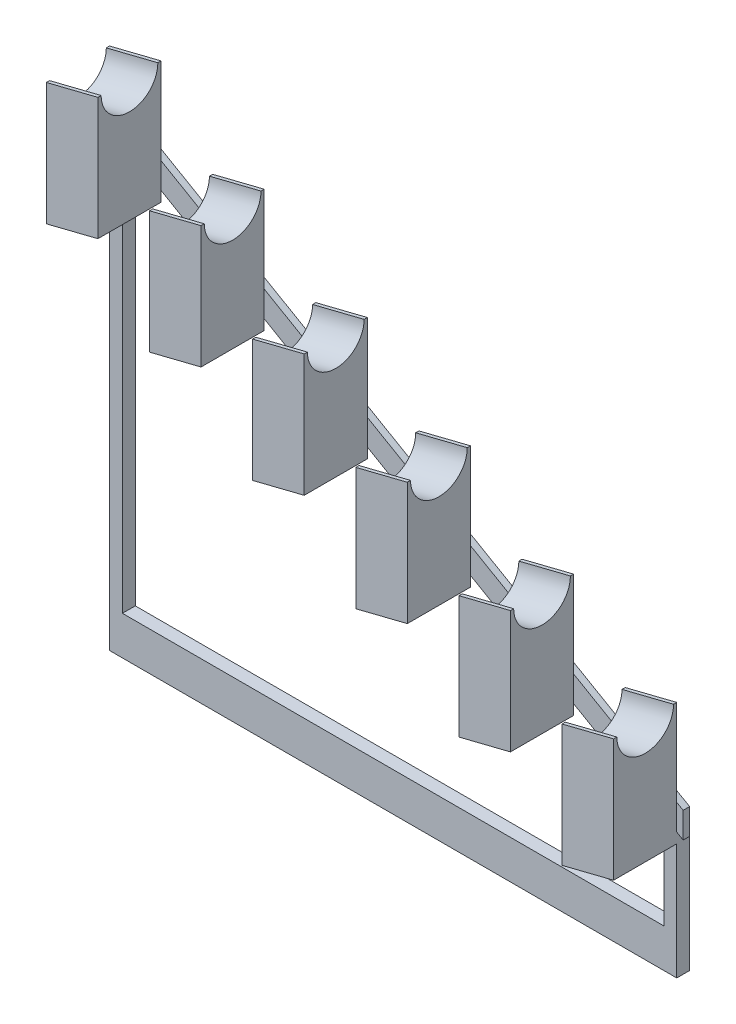
SolidWorks part; units mm, degrees
ref_plane "Front Plane" through (0, 0, 0) normal (0, 0, 1) x (1, 0, 0)
ref_plane "Top Plane" through (0, 0, 0) normal (0, 1, 0) x (1, 0, 0)
ref_plane "Right Plane" through (0, 0, 0) normal (1, 0, 0) x (0, 0, -1)
sketch "Sketch2" plane through (0, 0, 0) normal (1, 0, 0) x (0, 0, -1)
  line L2 (0, 0) -> (0, -84.6928) construction
  line L7 (-24.5, 0) -> (-22, 0)
  line L9 (-24.5, 0) -> (-24.5, -95)
  line L10 (-24.5, -95) -> (24.5, -95)
  line L11 (24.5, 0) -> (24.5, -95)
  line L12 (22, 0) -> (24.5, 0)
  arc A0 (-22, 0) -> (22, 0) centre (0, 0) ccw
  dimension "D1" = 22
  dimension "D3" = 95
  dimension "D4" = 2.5
  dimension "D2" = 49
  dimension "D5" = 2.5
sketch "Sketch3" plane through (0, 0, 0) normal (0, 0, 1) x (1, 0, 0)
  line L0 (0, 0) -> (-40, -10)
  dimension "D1" = 40
  dimension "D2" = 10
sweep "Sweep1" add profiles "Sketch2" path "Sketch3"
ref_plane "Plane2" through (0, -105, 0) normal (0, 1, 0) x (1, 0, 0)
sketch "Sketch7" plane through (0, 0, 24.5) normal (0, 0, 1) x (1, 0, 0)
  line L0 (5, -70) -> (-445, 189.8076)
  line L1 (-445, 189.8076) -> (-445, 169.8076)
  line L2 (-445, 169.8076) -> (5, -90)
  line L3 (5, -90) -> (5, -70)
  line L6 (0, 0) -> (0, -95) construction
  dimension "D1" = 60
  dimension "D2" = 450
  dimension "D3" = 20
  dimension "D4" = 70
  dimension "D5" = 5
extrude "Boss-Extrude1" add sketch "Sketch7" against normal blind 5 from surface starting at face at (-20, -52.5, -24.5)
pattern_linear "LPattern1" count 6 spacing 92.4 along (-0.866, 0.5, 0) of "Sweep1"
ref_plane "Plane3" through (0, 189.8076, 0) normal (0, 1, 0) x (1, 0, 0)
sketch "Sketch8" plane through (0, 189.8076, 0) normal (0, 1, 0) x (1, 0, 0)
  line L9 (-440.1037, 24.5) -> (-430.1037, 24.5)
  line L10 (-440.1037, 24.5) -> (-440.1037, 34.5)
  line L11 (-440.1037, 34.5) -> (-430.1037, 34.5)
  line L12 (-430.1037, 24.5) -> (-430.1037, 34.5)
  dimension "D1" = 10
  dimension "D2" = 10
extrude "Boss-Extrude2" add sketch "Sketch8" against normal blind 330 from offset 15 offset against normal yes
ref_plane "Plane4" through (0, -70, 0) normal (0, 1, 0) x (1, 0, 0)
sketch "Sketch11" plane through (0, -70, 0) normal (0, 1, 0) x (1, 0, 0)
  line L1 (0, 24.5) -> (-10, 24.5)
  line L2 (0, 24.5) -> (0, 34.5)
  line L3 (0, 34.5) -> (-10, 34.5)
  line L4 (-10, 24.5) -> (-10, 34.5)
  dimension "D1" = 10
  dimension "D2" = 10
extrude "Boss-Extrude5" add sketch "Sketch11" against normal up to surface (85.1924 mm away) up to face at (-435.1037, -155.1924, -29.5)
fillet "Fillet1" radius 20 2 edges at (-5, -70, -34.5) (-435.1037, 174.8076, -34.5)
sketch "Sketch12" plane through (0, 0, -34.5) normal (0, 0, -1) x (-1, 0, 0)
  line L0 (0, -155.1924) -> (440.1037, -155.1924)
  line L5 (0, -155.1924) -> (0, -185.1924)
  line L6 (440.1037, -155.1924) -> (440.1037, -185.1924)
  line L7 (0, -185.1924) -> (440.1037, -185.1924)
  dimension "D1" = 30
extrude "Boss-Extrude6" add sketch "Sketch12" against normal blind 10
